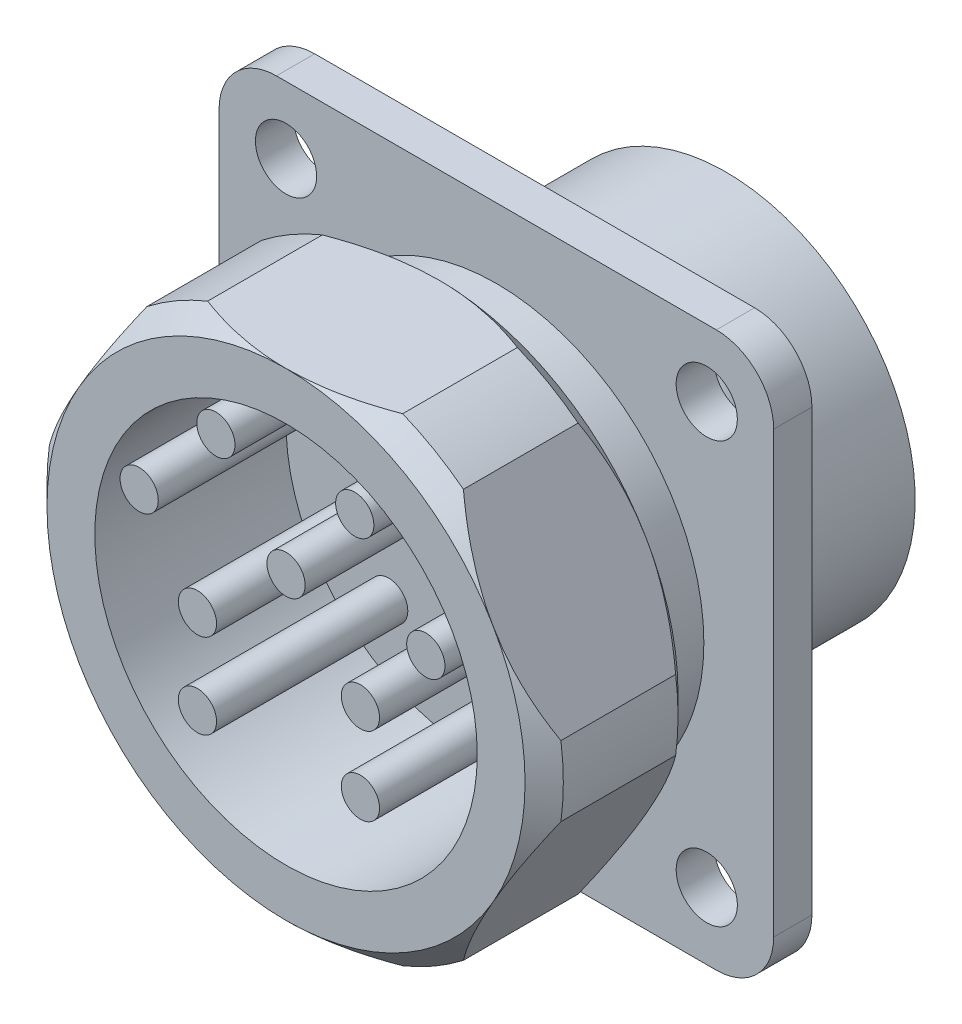
SolidWorks part; units mm, degrees
ref_plane "前视" through (0, 0, 0) normal (0, 0, 1) x (1, 0, 0)
ref_plane "上视" through (0, 0, 0) normal (0, 1, 0) x (1, 0, 0)
ref_plane "右视" through (0, 0, 0) normal (1, 0, 0) x (0, 0, -1)
sketch "草图1" plane through (0, 0, 0) normal (0, 0, 1) x (1, 0, 0)
  line L0 (0, 13.0471) -> (0, 0) construction
  line L1 (-11.5, -14.5) -> (11.5, -14.5)
  line L2 (-14.5, -11.5) -> (-14.5, 11.5)
  line L3 (-11.5, 14.5) -> (11.5, 14.5)
  line L4 (14.5, -11.5) -> (14.5, 11.5)
  line L5 (-14.5, -14.5) -> (14.5, 14.5) construction
  line L6 (-14.5, 14.5) -> (14.5, -14.5) construction
  line L7 (0, 0) -> (11.3985, 0) construction
  circle A0 centre (11, 11) radius 1.6
  circle A1 centre (-11, 11) radius 1.6
  circle A2 centre (-11, -11) radius 1.6
  circle A3 centre (11, -11) radius 1.6
  arc A4 (-11.5, -14.5) -> (-14.5, -11.5) centre (-11.5, -11.5) cw
  arc A5 (11.5, -14.5) -> (14.5, -11.5) centre (11.5, -11.5) ccw
  arc A6 (11.5, 14.5) -> (14.5, 11.5) centre (11.5, 11.5) cw
  arc A7 (-14.5, 11.5) -> (-11.5, 14.5) centre (-11.5, 11.5) cw
  point P0 (0, 0)
  dimension "D2" = 3.2
  dimension "D4" = 3
  dimension "D1" = 29
  dimension "D3" = 22
extrude "凸台-拉伸1" add sketch "草图1" against normal blind 2
sketch "草图2" plane through (0, 0, 0) normal (0, 0, 1) x (1, 0, 0)
  circle A0 centre (0, 0) radius 10.85
  dimension "D1" = 21.7
extrude "凸台-拉伸2" add sketch "草图2" along normal blind 3
sketch "草图3" plane through (0, 0, 3) normal (0, 0, 1) x (1, 0, 0)
  line L1 (13.3748, 1.8341) -> (8.2758, 10.6659)
  line L2 (5.099, 12.5) -> (-5.099, 12.5)
  line L3 (-8.2758, 10.6659) -> (-13.3748, 1.8341)
  line L4 (-13.3748, -1.8341) -> (-8.2758, -10.6659)
  line L5 (-5.099, -12.5) -> (5.099, -12.5)
  line L6 (8.2758, -10.6659) -> (13.3748, -1.8341)
  arc A0 (-5.099, 12.5) -> (-8.2758, 10.6659) centre (0, 0) ccw
  circle A1 centre (0, 0) radius 12.5 construction
  arc A2 (8.2758, 10.6659) -> (5.099, 12.5) centre (0, 0) ccw
  arc A3 (13.3748, -1.8341) -> (13.3748, 1.8341) centre (0, 0) ccw
  arc A4 (5.099, -12.5) -> (8.2758, -10.6659) centre (0, 0) ccw
  arc A5 (-8.2758, -10.6659) -> (-5.099, -12.5) centre (0, 0) ccw
  arc A6 (-13.3748, 1.8341) -> (-13.3748, -1.8341) centre (0, 0) ccw
  dimension "D1" = 27
  dimension "D2" = 25
extrude "凸台-拉伸3" add sketch "草图3" along normal blind 8
sketch "草图4" plane through (0, 0, -2) normal (0, 0, -1) x (-1, 0, 0)
  circle A0 centre (0, 0) radius 9.9
  dimension "D1" = 19.8
extrude "凸台-拉伸4" add sketch "草图4" along normal blind 10
chamfer "倒角1" distance 1 angle 45 6 edges at (-6.75, -11.6913, 3) (-13.5, 0, 3) (-6.75, 11.6913, 3) (6.75, 11.6913, 3) (6.75, -11.6913, 3) (13.5, 0, 3)
chamfer "倒角2" distance 1 angle 45 6 edges at (13.5, 0, 11) (6.75, 11.6913, 11) (6.75, -11.6913, 11) (-6.75, -11.6913, 11) (-6.75, 11.6913, 11) (-13.5, 0, 11)
sketch "草图5" plane through (0, 0, 11) normal (0, 0, 1) x (1, 0, 0)
  circle A0 centre (0, 0) radius 10
  circle A1 centre (-3.6693, 7.6976) radius 1
  circle A2 centre (3.5935, 7.6976) radius 1
  circle A3 centre (-7.6807, 3.1795) radius 1
  circle A4 centre (0, 3.1795) radius 1
  circle A5 centre (7.3093, 3.1795) radius 1
  circle A6 centre (-4.6321, -0.8741) radius 1
  circle A7 centre (3.889, -0.8741) radius 1
  circle A8 centre (-4.6321, -5.3077) radius 1
  circle A9 centre (3.889, -4.9699) radius 1
  dimension "D1" = 20
  dimension "D2" = 2
extrude "切除-拉伸1" cut sketch "草图5" against normal blind 10
